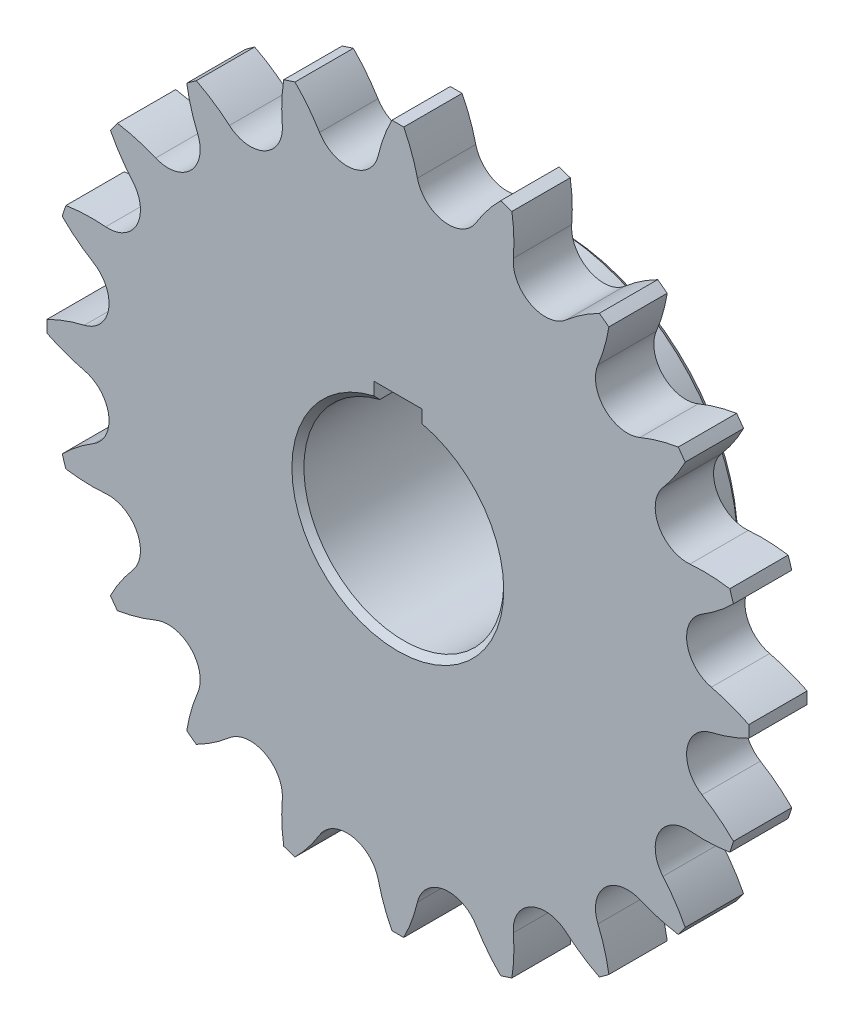
SolidWorks part; units mm, degrees
ref_plane "Front" through (0, 0, 0) normal (0, 0, 1) x (1, 0, 0)
ref_plane "Top" through (0, 0, 0) normal (0, 1, 0) x (1, 0, 0)
ref_plane "Right" through (0, 0, 0) normal (1, 0, 0) x (0, 0, -1)
sketch "Sketch1" plane through (0, 0, 0) normal (0, 0, 1) x (1, 0, 0)
  line L4 (0, -90.8046) -> (0, 90.8046) construction
  line L5 (-90.8046, 0) -> (90.8046, 0) construction
  line L6 (-1.75, -1.75) -> (1.75, 1.75)
  line L7 (-1.75, 1.75) -> (1.75, -1.75)
  circle A64 centre (0, 0) radius 73.2442 construction
  circle A65 centre (0, 0) radius 81.1842 construction
  arc A66 (76.1028, 19.5683) -> (78.425, 4.9065) centre (80.2631, 12.7124) ccw
  arc A67 (87.7921, 1.4821) -> (78.425, 4.9065) centre (68.8162, -35.9007) ccw
  arc A68 (83.9533, 25.7197) -> (83.0373, 28.5388) centre (0, 0) ccw
  arc A69 (76.1028, 19.5683) -> (83.9533, 25.7197) centre (54.3542, 55.4089) ccw
  arc A70 (66.3311, 42.1276) -> (73.0704, 28.901) centre (72.4064, 36.8929) ccw
  arc A71 (83.0373, 28.5388) -> (73.0704, 28.901) centre (76.542, -12.8782) ccw
  arc A72 (71.8965, 50.4039) -> (70.1542, 52.8019) centre (0, 0) ccw
  arc A73 (66.3311, 42.1276) -> (71.8965, 50.4039) centre (34.5716, 69.4934) ccw
  arc A74 (50.0665, 60.5632) -> (60.5632, 50.0665) centre (57.462, 57.462) ccw
  arc A75 (70.1542, 52.8019) -> (60.5632, 50.0665) centre (76.7754, 11.4049) ccw
  arc A76 (52.8019, 70.1542) -> (50.4039, 71.8965) centre (0, 0) ccw
  arc A77 (50.0665, 60.5632) -> (52.8019, 70.1542) centre (11.4049, 76.7754) ccw
  arc A78 (28.901, 73.0704) -> (42.1276, 66.3311) centre (36.8929, 72.4064) ccw
  arc A79 (50.4039, 71.8965) -> (42.1276, 66.3311) centre (69.4934, 34.5716) ccw
  arc A80 (28.5388, 83.0373) -> (25.7197, 83.9533) centre (0, 0) ccw
  arc A81 (28.901, 73.0704) -> (28.5388, 83.0373) centre (-12.8782, 76.542) ccw
  arc A82 (4.9065, 78.425) -> (19.5683, 76.1028) centre (12.7124, 80.2631) ccw
  arc A83 (25.7197, 83.9533) -> (19.5683, 76.1028) centre (55.4089, 54.3542) ccw
  arc A84 (1.4821, 87.7921) -> (-1.4821, 87.7921) centre (0, 0) ccw
  arc A85 (4.9065, 78.425) -> (1.4821, 87.7921) centre (-35.9007, 68.8162) ccw
  arc A86 (-19.5683, 76.1028) -> (-4.9065, 78.425) centre (-12.7124, 80.2631) ccw
  arc A87 (-1.4821, 87.7921) -> (-4.9065, 78.425) centre (35.9007, 68.8162) ccw
  arc A88 (-25.7197, 83.9533) -> (-28.5388, 83.0373) centre (0, 0) ccw
  arc A89 (-19.5683, 76.1028) -> (-25.7197, 83.9533) centre (-55.4089, 54.3542) ccw
  arc A90 (-42.1276, 66.3311) -> (-28.901, 73.0704) centre (-36.8929, 72.4064) ccw
  arc A91 (-28.5388, 83.0373) -> (-28.901, 73.0704) centre (12.8782, 76.542) ccw
  arc A92 (-50.4039, 71.8965) -> (-52.8019, 70.1542) centre (0, 0) ccw
  arc A93 (-42.1276, 66.3311) -> (-50.4039, 71.8965) centre (-69.4934, 34.5716) ccw
  arc A94 (-60.5632, 50.0665) -> (-50.0665, 60.5632) centre (-57.462, 57.462) ccw
  arc A95 (-52.8019, 70.1542) -> (-50.0665, 60.5632) centre (-11.4049, 76.7754) ccw
  arc A96 (-70.1542, 52.8019) -> (-71.8965, 50.4039) centre (0, 0) ccw
  arc A97 (-60.5632, 50.0665) -> (-70.1542, 52.8019) centre (-76.7754, 11.4049) ccw
  arc A98 (-73.0704, 28.901) -> (-66.3311, 42.1276) centre (-72.4064, 36.8929) ccw
  arc A99 (-71.8965, 50.4039) -> (-66.3311, 42.1276) centre (-34.5716, 69.4934) ccw
  arc A100 (-83.0373, 28.5388) -> (-83.9533, 25.7197) centre (0, 0) ccw
  arc A101 (-73.0704, 28.901) -> (-83.0373, 28.5388) centre (-76.542, -12.8782) ccw
  arc A102 (-78.425, 4.9065) -> (-76.1028, 19.5683) centre (-80.2631, 12.7124) ccw
  arc A103 (-83.9533, 25.7197) -> (-76.1028, 19.5683) centre (-54.3542, 55.4089) ccw
  arc A104 (-87.7921, 1.4821) -> (-87.7921, -1.4821) centre (0, 0) ccw
  arc A105 (-78.425, 4.9065) -> (-87.7921, 1.4821) centre (-68.8162, -35.9007) ccw
  arc A106 (-76.1028, -19.5683) -> (-78.425, -4.9065) centre (-80.2631, -12.7124) ccw
  arc A107 (-87.7921, -1.4821) -> (-78.425, -4.9065) centre (-68.8162, 35.9007) ccw
  arc A108 (-83.9533, -25.7197) -> (-83.0373, -28.5388) centre (0, 0) ccw
  arc A109 (-76.1028, -19.5683) -> (-83.9533, -25.7197) centre (-54.3542, -55.4089) ccw
  arc A110 (-66.3311, -42.1276) -> (-73.0704, -28.901) centre (-72.4064, -36.8929) ccw
  arc A111 (-83.0373, -28.5388) -> (-73.0704, -28.901) centre (-76.542, 12.8782) ccw
  arc A112 (-71.8965, -50.4039) -> (-70.1542, -52.8019) centre (0, 0) ccw
  arc A113 (-66.3311, -42.1276) -> (-71.8965, -50.4039) centre (-34.5716, -69.4934) ccw
  arc A114 (-50.0665, -60.5632) -> (-60.5632, -50.0665) centre (-57.462, -57.462) ccw
  arc A115 (-70.1542, -52.8019) -> (-60.5632, -50.0665) centre (-76.7754, -11.4049) ccw
  arc A116 (-52.8019, -70.1542) -> (-50.4039, -71.8965) centre (0, 0) ccw
  arc A117 (-50.0665, -60.5632) -> (-52.8019, -70.1542) centre (-11.4049, -76.7754) ccw
  arc A118 (-28.901, -73.0704) -> (-42.1276, -66.3311) centre (-36.8929, -72.4064) ccw
  arc A119 (-50.4039, -71.8965) -> (-42.1276, -66.3311) centre (-69.4934, -34.5716) ccw
  arc A120 (-28.5388, -83.0373) -> (-25.7197, -83.9533) centre (0, 0) ccw
  arc A121 (-28.901, -73.0704) -> (-28.5388, -83.0373) centre (12.8782, -76.542) ccw
  arc A122 (-4.9065, -78.425) -> (-19.5683, -76.1028) centre (-12.7124, -80.2631) ccw
  arc A123 (-25.7197, -83.9533) -> (-19.5683, -76.1028) centre (-55.4089, -54.3542) ccw
  arc A124 (-1.4821, -87.7921) -> (1.4821, -87.7921) centre (0, 0) ccw
  arc A125 (-4.9065, -78.425) -> (-1.4821, -87.7921) centre (35.9007, -68.8162) ccw
  arc A126 (19.5683, -76.1028) -> (4.9065, -78.425) centre (12.7124, -80.2631) ccw
  arc A127 (1.4821, -87.7921) -> (4.9065, -78.425) centre (-35.9007, -68.8162) ccw
  arc A128 (25.7197, -83.9533) -> (28.5388, -83.0373) centre (0, 0) ccw
  arc A129 (19.5683, -76.1028) -> (25.7197, -83.9533) centre (55.4089, -54.3542) ccw
  arc A130 (42.1276, -66.3311) -> (28.901, -73.0704) centre (36.8929, -72.4064) ccw
  arc A131 (28.5388, -83.0373) -> (28.901, -73.0704) centre (-12.8782, -76.542) ccw
  arc A132 (50.4039, -71.8965) -> (52.8019, -70.1542) centre (0, 0) ccw
  arc A133 (42.1276, -66.3311) -> (50.4039, -71.8965) centre (69.4934, -34.5716) ccw
  arc A134 (60.5632, -50.0665) -> (50.0665, -60.5632) centre (57.462, -57.462) ccw
  arc A135 (52.8019, -70.1542) -> (50.0665, -60.5632) centre (11.4049, -76.7754) ccw
  arc A136 (70.1542, -52.8019) -> (71.8965, -50.4039) centre (0, 0) ccw
  arc A137 (60.5632, -50.0665) -> (70.1542, -52.8019) centre (76.7754, -11.4049) ccw
  arc A138 (73.0704, -28.901) -> (66.3311, -42.1276) centre (72.4064, -36.8929) ccw
  arc A139 (71.8965, -50.4039) -> (66.3311, -42.1276) centre (34.5716, -69.4934) ccw
  arc A140 (83.0373, -28.5388) -> (83.9533, -25.7197) centre (0, 0) ccw
  arc A141 (73.0704, -28.901) -> (83.0373, -28.5388) centre (76.542, 12.8782) ccw
  arc A142 (78.425, -4.9065) -> (76.1028, -19.5683) centre (80.2631, -12.7124) ccw
  arc A143 (83.9533, -25.7197) -> (76.1028, -19.5683) centre (54.3542, -55.4089) ccw
  arc A144 (87.7921, -1.4821) -> (87.7921, 1.4821) centre (0, 0) ccw
  arc A145 (78.425, -4.9065) -> (87.7921, -1.4821) centre (68.8162, 35.9007) ccw
  circle A146 centre (0, 0) radius 25
  circle A147 centre (0, 0) radius 1.75
sketch "Sketch2" plane through (0, 0, 0) normal (0, 0, 1) x (1, 0, 0)
  circle A0 centre (0, 0) radius 25 construction
  arc A123 (-52.8019, 70.1542) -> (-50.0665, 60.5632) centre (-11.4049, 76.7754) ccw construction
  arc A124 (-60.5632, 50.0665) -> (-50.0665, 60.5632) centre (-57.462, 57.462) ccw construction
  arc A125 (-60.5632, 50.0665) -> (-70.1542, 52.8019) centre (-76.7754, 11.4049) ccw construction
  arc A126 (-70.1542, 52.8019) -> (-71.8965, 50.4039) centre (0, 0) ccw construction
  arc A127 (-71.8965, 50.4039) -> (-66.3311, 42.1276) centre (-34.5716, 69.4934) ccw construction
  arc A128 (-73.0704, 28.901) -> (-66.3311, 42.1276) centre (-72.4064, 36.8929) ccw construction
  arc A129 (-73.0704, 28.901) -> (-83.0373, 28.5388) centre (-76.542, -12.8782) ccw construction
  arc A130 (-83.0373, 28.5388) -> (-83.9533, 25.7197) centre (0, 0) ccw construction
  arc A131 (-83.9533, 25.7197) -> (-76.1028, 19.5683) centre (-54.3542, 55.4089) ccw construction
  arc A132 (-78.425, 4.9065) -> (-76.1028, 19.5683) centre (-80.2631, 12.7124) ccw construction
  arc A133 (-78.425, 4.9065) -> (-87.7921, 1.4821) centre (-68.8162, -35.9007) ccw construction
  arc A134 (-87.7921, 1.4821) -> (-87.7921, -1.4821) centre (0, 0) ccw construction
  arc A135 (-87.7921, -1.4821) -> (-78.425, -4.9065) centre (-68.8162, 35.9007) ccw construction
  arc A136 (-76.1028, -19.5683) -> (-78.425, -4.9065) centre (-80.2631, -12.7124) ccw construction
  arc A137 (-76.1028, -19.5683) -> (-83.9533, -25.7197) centre (-54.3542, -55.4089) ccw construction
  arc A138 (-83.9533, -25.7197) -> (-83.0373, -28.5388) centre (0, 0) ccw construction
  arc A139 (-83.0373, -28.5388) -> (-73.0704, -28.901) centre (-76.542, 12.8782) ccw construction
  arc A140 (-66.3311, -42.1276) -> (-73.0704, -28.901) centre (-72.4064, -36.8929) ccw construction
  arc A141 (-66.3311, -42.1276) -> (-71.8965, -50.4039) centre (-34.5716, -69.4934) ccw construction
  arc A142 (-71.8965, -50.4039) -> (-70.1542, -52.8019) centre (0, 0) ccw construction
  arc A143 (-70.1542, -52.8019) -> (-60.5632, -50.0665) centre (-76.7754, -11.4049) ccw construction
  arc A144 (-50.0665, -60.5632) -> (-60.5632, -50.0665) centre (-57.462, -57.462) ccw construction
  arc A145 (-50.0665, -60.5632) -> (-52.8019, -70.1542) centre (-11.4049, -76.7754) ccw construction
  arc A146 (-52.8019, -70.1542) -> (-50.4039, -71.8965) centre (0, 0) ccw construction
  arc A147 (-50.4039, -71.8965) -> (-42.1276, -66.3311) centre (-69.4934, -34.5716) ccw construction
  arc A148 (-28.901, -73.0704) -> (-42.1276, -66.3311) centre (-36.8929, -72.4064) ccw construction
  arc A149 (-28.901, -73.0704) -> (-28.5388, -83.0373) centre (12.8782, -76.542) ccw construction
  arc A150 (-28.5388, -83.0373) -> (-25.7197, -83.9533) centre (0, 0) ccw construction
  arc A151 (-25.7197, -83.9533) -> (-19.5683, -76.1028) centre (-55.4089, -54.3542) ccw construction
  arc A152 (-4.9065, -78.425) -> (-19.5683, -76.1028) centre (-12.7124, -80.2631) ccw construction
  arc A153 (-4.9065, -78.425) -> (-1.4821, -87.7921) centre (35.9007, -68.8162) ccw construction
  arc A154 (-1.4821, -87.7921) -> (1.4821, -87.7921) centre (0, 0) ccw construction
  arc A155 (1.4821, -87.7921) -> (4.9065, -78.425) centre (-35.9007, -68.8162) ccw construction
  arc A156 (19.5683, -76.1028) -> (4.9065, -78.425) centre (12.7124, -80.2631) ccw construction
  arc A157 (19.5683, -76.1028) -> (25.7197, -83.9533) centre (55.4089, -54.3542) ccw construction
  arc A158 (25.7197, -83.9533) -> (28.5388, -83.0373) centre (0, 0) ccw construction
  arc A159 (28.5388, -83.0373) -> (28.901, -73.0704) centre (-12.8782, -76.542) ccw construction
  arc A160 (42.1276, -66.3311) -> (28.901, -73.0704) centre (36.8929, -72.4064) ccw construction
  arc A161 (42.1276, -66.3311) -> (50.4039, -71.8965) centre (69.4934, -34.5716) ccw construction
  arc A162 (50.4039, -71.8965) -> (52.8019, -70.1542) centre (0, 0) ccw construction
  arc A163 (52.8019, -70.1542) -> (50.0665, -60.5632) centre (11.4049, -76.7754) ccw construction
  arc A164 (60.5632, -50.0665) -> (50.0665, -60.5632) centre (57.462, -57.462) ccw construction
  arc A165 (60.5632, -50.0665) -> (70.1542, -52.8019) centre (76.7754, -11.4049) ccw construction
  arc A166 (70.1542, -52.8019) -> (71.8965, -50.4039) centre (0, 0) ccw construction
  arc A167 (71.8965, -50.4039) -> (66.3311, -42.1276) centre (34.5716, -69.4934) ccw construction
  arc A168 (73.0704, -28.901) -> (66.3311, -42.1276) centre (72.4064, -36.8929) ccw construction
  arc A169 (73.0704, -28.901) -> (83.0373, -28.5388) centre (76.542, 12.8782) ccw construction
  arc A170 (83.0373, -28.5388) -> (83.9533, -25.7197) centre (0, 0) ccw construction
  arc A171 (83.9533, -25.7197) -> (76.1028, -19.5683) centre (54.3542, -55.4089) ccw construction
  arc A172 (78.425, -4.9065) -> (76.1028, -19.5683) centre (80.2631, -12.7124) ccw construction
  arc A173 (78.425, -4.9065) -> (87.7921, -1.4821) centre (68.8162, 35.9007) ccw construction
  arc A174 (87.7921, -1.4821) -> (87.7921, 1.4821) centre (0, 0) ccw construction
  arc A175 (87.7921, 1.4821) -> (78.425, 4.9065) centre (68.8162, -35.9007) ccw construction
  arc A176 (76.1028, 19.5683) -> (78.425, 4.9065) centre (80.2631, 12.7124) ccw construction
  arc A177 (76.1028, 19.5683) -> (83.9533, 25.7197) centre (54.3542, 55.4089) ccw construction
  arc A178 (83.9533, 25.7197) -> (83.0373, 28.5388) centre (0, 0) ccw construction
  arc A179 (83.0373, 28.5388) -> (73.0704, 28.901) centre (76.542, -12.8782) ccw construction
  arc A180 (66.3311, 42.1276) -> (73.0704, 28.901) centre (72.4064, 36.8929) ccw construction
  arc A181 (66.3311, 42.1276) -> (71.8965, 50.4039) centre (34.5716, 69.4934) ccw construction
  arc A182 (71.8965, 50.4039) -> (70.1542, 52.8019) centre (0, 0) ccw construction
  arc A183 (70.1542, 52.8019) -> (60.5632, 50.0665) centre (76.7754, 11.4049) ccw construction
  arc A184 (50.0665, 60.5632) -> (60.5632, 50.0665) centre (57.462, 57.462) ccw construction
  arc A185 (50.0665, 60.5632) -> (52.8019, 70.1542) centre (11.4049, 76.7754) ccw construction
  arc A186 (52.8019, 70.1542) -> (50.4039, 71.8965) centre (0, 0) ccw construction
  arc A187 (50.4039, 71.8965) -> (42.1276, 66.3311) centre (69.4934, 34.5716) ccw construction
  arc A188 (28.901, 73.0704) -> (42.1276, 66.3311) centre (36.8929, 72.4064) ccw construction
  arc A189 (28.901, 73.0704) -> (28.5388, 83.0373) centre (-12.8782, 76.542) ccw construction
  arc A190 (28.5388, 83.0373) -> (25.7197, 83.9533) centre (0, 0) ccw construction
  arc A191 (25.7197, 83.9533) -> (19.5683, 76.1028) centre (55.4089, 54.3542) ccw construction
  arc A192 (4.9065, 78.425) -> (19.5683, 76.1028) centre (12.7124, 80.2631) ccw construction
  arc A193 (4.9065, 78.425) -> (1.4821, 87.7921) centre (-35.9007, 68.8162) ccw construction
  arc A194 (1.4821, 87.7921) -> (-1.4821, 87.7921) centre (0, 0) ccw construction
  arc A195 (-1.4821, 87.7921) -> (-4.9065, 78.425) centre (35.9007, 68.8162) ccw construction
  arc A196 (-19.5683, 76.1028) -> (-4.9065, 78.425) centre (-12.7124, 80.2631) ccw construction
  arc A197 (-19.5683, 76.1028) -> (-25.7197, 83.9533) centre (-55.4089, 54.3542) ccw construction
  arc A198 (-25.7197, 83.9533) -> (-28.5388, 83.0373) centre (0, 0) ccw construction
  arc A199 (-28.5388, 83.0373) -> (-28.901, 73.0704) centre (12.8782, 76.542) ccw construction
  arc A200 (-42.1276, 66.3311) -> (-28.901, 73.0704) centre (-36.8929, 72.4064) ccw construction
  arc A201 (-42.1276, 66.3311) -> (-50.4039, 71.8965) centre (-69.4934, 34.5716) ccw construction
  arc A202 (-50.4039, 71.8965) -> (-52.8019, 70.1542) centre (0, 0) ccw construction
  circle A203 centre (0, 0) radius 25
  arc A204 (-52.8019, 70.1542) -> (-50.0665, 60.5632) centre (-11.4049, 76.7754) ccw
  arc A205 (-60.5632, 50.0665) -> (-50.0665, 60.5632) centre (-57.462, 57.462) ccw
  arc A206 (-60.5632, 50.0665) -> (-70.1542, 52.8019) centre (-76.7754, 11.4049) ccw
  arc A207 (-70.1542, 52.8019) -> (-71.8965, 50.4039) centre (0, 0) ccw
  arc A208 (-71.8965, 50.4039) -> (-66.3311, 42.1276) centre (-34.5716, 69.4934) ccw
  arc A209 (-73.0704, 28.901) -> (-66.3311, 42.1276) centre (-72.4064, 36.8929) ccw
  arc A210 (-73.0704, 28.901) -> (-83.0373, 28.5388) centre (-76.542, -12.8782) ccw
  arc A211 (-83.0373, 28.5388) -> (-83.9533, 25.7197) centre (0, 0) ccw
  arc A212 (-83.9533, 25.7197) -> (-76.1028, 19.5683) centre (-54.3542, 55.4089) ccw
  arc A213 (-78.425, 4.9065) -> (-76.1028, 19.5683) centre (-80.2631, 12.7124) ccw
  arc A214 (-78.425, 4.9065) -> (-87.7921, 1.4821) centre (-68.8162, -35.9007) ccw
  arc A215 (-87.7921, 1.4821) -> (-87.7921, -1.4821) centre (0, 0) ccw
  arc A216 (-87.7921, -1.4821) -> (-78.425, -4.9065) centre (-68.8162, 35.9007) ccw
  arc A217 (-76.1028, -19.5683) -> (-78.425, -4.9065) centre (-80.2631, -12.7124) ccw
  arc A218 (-76.1028, -19.5683) -> (-83.9533, -25.7197) centre (-54.3542, -55.4089) ccw
  arc A219 (-83.9533, -25.7197) -> (-83.0373, -28.5388) centre (0, 0) ccw
  arc A220 (-83.0373, -28.5388) -> (-73.0704, -28.901) centre (-76.542, 12.8782) ccw
  arc A221 (-66.3311, -42.1276) -> (-73.0704, -28.901) centre (-72.4064, -36.8929) ccw
  arc A222 (-66.3311, -42.1276) -> (-71.8965, -50.4039) centre (-34.5716, -69.4934) ccw
  arc A223 (-71.8965, -50.4039) -> (-70.1542, -52.8019) centre (0, 0) ccw
  arc A224 (-70.1542, -52.8019) -> (-60.5632, -50.0665) centre (-76.7754, -11.4049) ccw
  arc A225 (-50.0665, -60.5632) -> (-60.5632, -50.0665) centre (-57.462, -57.462) ccw
  arc A226 (-50.0665, -60.5632) -> (-52.8019, -70.1542) centre (-11.4049, -76.7754) ccw
  arc A227 (-52.8019, -70.1542) -> (-50.4039, -71.8965) centre (0, 0) ccw
  arc A228 (-50.4039, -71.8965) -> (-42.1276, -66.3311) centre (-69.4934, -34.5716) ccw
  arc A229 (-28.901, -73.0704) -> (-42.1276, -66.3311) centre (-36.8929, -72.4064) ccw
  arc A230 (-28.901, -73.0704) -> (-28.5388, -83.0373) centre (12.8782, -76.542) ccw
  arc A231 (-28.5388, -83.0373) -> (-25.7197, -83.9533) centre (0, 0) ccw
  arc A232 (-25.7197, -83.9533) -> (-19.5683, -76.1028) centre (-55.4089, -54.3542) ccw
  arc A233 (-4.9065, -78.425) -> (-19.5683, -76.1028) centre (-12.7124, -80.2631) ccw
  arc A234 (-4.9065, -78.425) -> (-1.4821, -87.7921) centre (35.9007, -68.8162) ccw
  arc A235 (-1.4821, -87.7921) -> (1.4821, -87.7921) centre (0, 0) ccw
  arc A236 (1.4821, -87.7921) -> (4.9065, -78.425) centre (-35.9007, -68.8162) ccw
  arc A237 (19.5683, -76.1028) -> (4.9065, -78.425) centre (12.7124, -80.2631) ccw
  arc A238 (19.5683, -76.1028) -> (25.7197, -83.9533) centre (55.4089, -54.3542) ccw
  arc A239 (25.7197, -83.9533) -> (28.5388, -83.0373) centre (0, 0) ccw
  arc A240 (28.5388, -83.0373) -> (28.901, -73.0704) centre (-12.8782, -76.542) ccw
  arc A241 (42.1276, -66.3311) -> (28.901, -73.0704) centre (36.8929, -72.4064) ccw
  arc A242 (42.1276, -66.3311) -> (50.4039, -71.8965) centre (69.4934, -34.5716) ccw
  arc A243 (50.4039, -71.8965) -> (52.8019, -70.1542) centre (0, 0) ccw
  arc A244 (52.8019, -70.1542) -> (50.0665, -60.5632) centre (11.4049, -76.7754) ccw
  arc A245 (60.5632, -50.0665) -> (50.0665, -60.5632) centre (57.462, -57.462) ccw
  arc A246 (60.5632, -50.0665) -> (70.1542, -52.8019) centre (76.7754, -11.4049) ccw
  arc A247 (70.1542, -52.8019) -> (71.8965, -50.4039) centre (0, 0) ccw
  arc A248 (71.8965, -50.4039) -> (66.3311, -42.1276) centre (34.5716, -69.4934) ccw
  arc A249 (73.0704, -28.901) -> (66.3311, -42.1276) centre (72.4064, -36.8929) ccw
  arc A250 (73.0704, -28.901) -> (83.0373, -28.5388) centre (76.542, 12.8782) ccw
  arc A251 (83.0373, -28.5388) -> (83.9533, -25.7197) centre (0, 0) ccw
  arc A252 (83.9533, -25.7197) -> (76.1028, -19.5683) centre (54.3542, -55.4089) ccw
  arc A253 (78.425, -4.9065) -> (76.1028, -19.5683) centre (80.2631, -12.7124) ccw
  arc A254 (78.425, -4.9065) -> (87.7921, -1.4821) centre (68.8162, 35.9007) ccw
  arc A255 (87.7921, -1.4821) -> (87.7921, 1.4821) centre (0, 0) ccw
  arc A256 (87.7921, 1.4821) -> (78.425, 4.9065) centre (68.8162, -35.9007) ccw
  arc A257 (76.1028, 19.5683) -> (78.425, 4.9065) centre (80.2631, 12.7124) ccw
  arc A258 (76.1028, 19.5683) -> (83.9533, 25.7197) centre (54.3542, 55.4089) ccw
  arc A259 (83.9533, 25.7197) -> (83.0373, 28.5388) centre (0, 0) ccw
  arc A260 (83.0373, 28.5388) -> (73.0704, 28.901) centre (76.542, -12.8782) ccw
  arc A261 (66.3311, 42.1276) -> (73.0704, 28.901) centre (72.4064, 36.8929) ccw
  arc A262 (66.3311, 42.1276) -> (71.8965, 50.4039) centre (34.5716, 69.4934) ccw
  arc A263 (71.8965, 50.4039) -> (70.1542, 52.8019) centre (0, 0) ccw
  arc A264 (70.1542, 52.8019) -> (60.5632, 50.0665) centre (76.7754, 11.4049) ccw
  arc A265 (50.0665, 60.5632) -> (60.5632, 50.0665) centre (57.462, 57.462) ccw
  arc A266 (50.0665, 60.5632) -> (52.8019, 70.1542) centre (11.4049, 76.7754) ccw
  arc A267 (52.8019, 70.1542) -> (50.4039, 71.8965) centre (0, 0) ccw
  arc A268 (50.4039, 71.8965) -> (42.1276, 66.3311) centre (69.4934, 34.5716) ccw
  arc A269 (28.901, 73.0704) -> (42.1276, 66.3311) centre (36.8929, 72.4064) ccw
  arc A270 (28.901, 73.0704) -> (28.5388, 83.0373) centre (-12.8782, 76.542) ccw
  arc A271 (28.5388, 83.0373) -> (25.7197, 83.9533) centre (0, 0) ccw
  arc A272 (25.7197, 83.9533) -> (19.5683, 76.1028) centre (55.4089, 54.3542) ccw
  arc A273 (4.9065, 78.425) -> (19.5683, 76.1028) centre (12.7124, 80.2631) ccw
  arc A274 (4.9065, 78.425) -> (1.4821, 87.7921) centre (-35.9007, 68.8162) ccw
  arc A275 (1.4821, 87.7921) -> (-1.4821, 87.7921) centre (0, 0) ccw
  arc A276 (-1.4821, 87.7921) -> (-4.9065, 78.425) centre (35.9007, 68.8162) ccw
  arc A277 (-19.5683, 76.1028) -> (-4.9065, 78.425) centre (-12.7124, 80.2631) ccw
  arc A278 (-19.5683, 76.1028) -> (-25.7197, 83.9533) centre (-55.4089, 54.3542) ccw
  arc A279 (-25.7197, 83.9533) -> (-28.5388, 83.0373) centre (0, 0) ccw
  arc A280 (-28.5388, 83.0373) -> (-28.901, 73.0704) centre (12.8782, 76.542) ccw
  arc A281 (-42.1276, 66.3311) -> (-28.901, 73.0704) centre (-36.8929, 72.4064) ccw
  arc A282 (-42.1276, 66.3311) -> (-50.4039, 71.8965) centre (-69.4934, 34.5716) ccw
  arc A283 (-50.4039, 71.8965) -> (-52.8019, 70.1542) centre (0, 0) ccw
extrude "Boss-Extrude1" add sketch "Sketch2" along normal blind 14.6
sketch "Sketch3" plane through (0, 0, 14.6) normal (0, 0, -1) x (-1, 0, 0)
  circle A0 centre (0, 0) radius 46.5
  circle A1 centre (0, 0) radius 25
  dimension "D1" = 50
  dimension "D2" = 93
extrude "Boss-Extrude2" add sketch "Sketch3" along normal blind 40
sketch "Sketch6" plane through (0, 0, -25.4) normal (0, 0, -1) x (-1, 0, 0)
  line L0 (0, 0) -> (0, 12.4127) construction
  line L5 (0, -25) -> (29.0973, -25) construction
  line L11 (6, 11.2065) -> (-6, 11.2065)
  line L12 (6, 11.2065) -> (6, 29)
  line L13 (6, 29) -> (-6, 29)
  line L14 (-6, 11.2065) -> (-6, 29)
  line L15 (6, 11.2065) -> (-6, 29) construction
  line L16 (6, 29) -> (-6, 11.2065) construction
  circle A0 centre (0, 0) radius 25 construction
  point P8 (0, 20.1033)
  dimension "D1" = 12
  dimension "D2" = 54
extrude "Cut-Extrude1" cut sketch "Sketch6" against normal blind 64 contours L12 L13 L14 L11
chamfer "Chamfer1" distance 1.5 angle 45 6 edges at (0, -25, -25.4) (-46.5, 0, -25.4) (-6, 26.6347, -25.4) (0, 29, -25.4) (6, 26.6347, -25.4) (0, -25, 14.6)
chamfer "Chamfer2" distance 8 angle 45 1 edges at (46.5, 0, 0)
